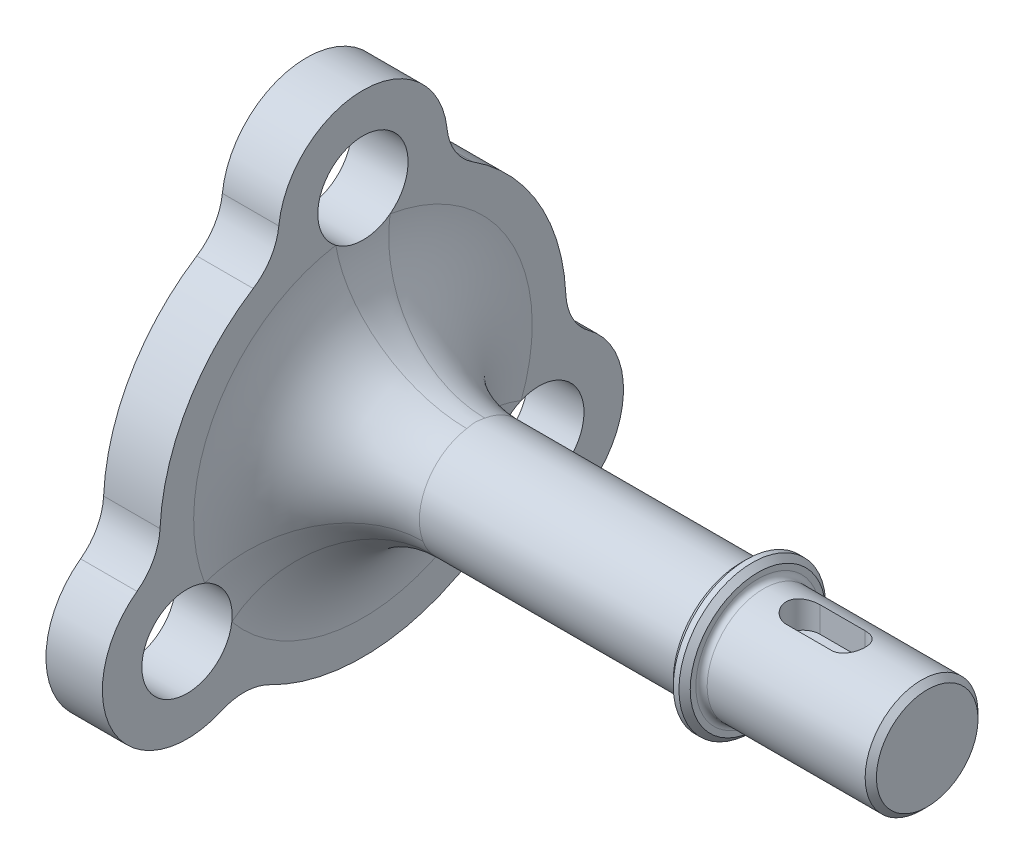
SolidWorks part; units mm, degrees
ref_plane "Front Plane" through (0, 0, 0) normal (0, 0, 1) x (1, 0, 0)
ref_plane "Top Plane" through (0, 0, 0) normal (0, 1, 0) x (1, 0, 0)
ref_plane "Right Plane" through (0, 0, 0) normal (1, 0, 0) x (0, 0, -1)
sketch "Sketch1" plane through (0, 0, 0) normal (1, 0, 0) x (0, 0, -1)
  line L0 (-15.5885, -9) -> (0, 18) construction
  line L1 (0, 18) -> (15.5885, -9) construction
  line L2 (15.5885, -9) -> (-13.3467, -9) construction
  circle A1 centre (0, 18) radius 4
  arc A2 (7.4559, 18.8125) -> (-7.4559, 18.8125) centre (0, 18) ccw
  arc A3 (12.5642, -15.8632) -> (20.02, -2.9493) centre (15.5885, -9) ccw
  circle A4 centre (15.5885, -9) radius 4
  arc A5 (-20.02, -2.9493) -> (-12.5642, -15.8632) centre (-15.5885, -9) ccw
  circle A6 centre (-15.5885, -9) radius 4
  arc A7 (-9.725, 15.1467) -> (-17.98, 0.8488) centre (0, 0) ccw
  arc A8 (-8.2549, -15.9955) -> (8.2549, -15.9955) centre (0, 0) ccw
  arc A9 (-7.4559, 18.8125) -> (-9.725, 15.1467) centre (-12.4264, 19.3542) cw
  arc A10 (17.98, 0.8488) -> (9.725, 15.1467) centre (0, 0) ccw
  arc A11 (20.02, -2.9493) -> (17.98, 0.8488) centre (22.9744, 1.0845) cw
  arc A12 (-20.02, -2.9493) -> (-17.98, 0.8488) centre (-22.9744, 1.0845) ccw
  arc A13 (12.5642, -15.8632) -> (8.2549, -15.9955) centre (10.548, -20.4387) ccw
  arc A14 (-12.5642, -15.8632) -> (-8.2549, -15.9955) centre (-10.548, -20.4387) cw
  arc A15 (7.4559, 18.8125) -> (9.725, 15.1467) centre (12.4264, 19.3542) ccw
  point P15 (0, 0)
  point P19 (-7.3354, 16.4375)
  point P22 (17.903, -1.8661)
  point P29 (-10.5676, -14.5714)
  dimension "D2" = 15
  dimension "D3" = 8
  dimension "D6" = 5
  dimension "D7" = 5
  dimension "D5" = 31.1769
  dimension "D4" = 3
extrude "Boss-Extrude1" add sketch "Sketch1" along normal blind 5
sketch "Sketch2" plane through (5, 0, 0) normal (1, 0, 0) x (0, 0, -1)
  circle A0 centre (0, 0) radius 5
  dimension "D1" = 10
extrude "Boss-Extrude2" add sketch "Sketch2" along normal blind 50
sketch "Sketch3" plane through (0, 0, 0) normal (0, 1, 0) x (1, 0, 0)
  line L0 (55, -5) -> (55, 5) construction
  line L1 (38.5, 6.5) -> (40, 6.5)
  line L2 (38.5, 6.5) -> (38.5, 5)
  line L3 (38.5, 5) -> (40, 5)
  line L4 (40, 6.5) -> (40, 5)
  line L5 (38.5, 6.5) -> (40, 5) construction
  line L6 (38.5, 5) -> (40, 6.5) construction
  line L7 (5, 0) -> (55, 0) construction
  line L8 (5, -7.4559) -> (5, 7.4559) construction
  point P0 (39.25, 5.75)
  dimension "D1" = 15
  dimension "D2" = 1.5
  dimension "D3" = 1.5
  dimension "D4" = 5
revolve "Revolve1" add sketch "Sketch3" angle 360 about L7
ref_plane "Plane1" through (0, 5, 0) normal (0, 1, 0) x (1, 0, 0)
sketch "Sketch4" plane through (0, 5, 0) normal (0, 1, 0) x (1, 0, 0)
  line L0 (44, 0) -> (48, 0) construction
  line L5 (44, 1.5) -> (48, 1.5)
  line L6 (44, -1.5) -> (48, -1.5)
  line L7 (55, 5) -> (40, 5) construction
  line L8 (55, -5) -> (55, 5) construction
  arc A2 (44, 1.5) -> (44, -1.5) centre (44, 0) ccw
  arc A3 (48, -1.5) -> (48, 1.5) centre (48, 0) ccw
  point P3 (46, 0)
  dimension "D1" = 1.5
  dimension "D2" = 4
  dimension "D3" = 5
  dimension "D4" = 9
extrude "Cut-Extrude1" cut sketch "Sketch4" against normal blind 2.5
fillet "Fillet2" radius 0.5 2 edges at (38.5, 0, -5) (40, 0, 5)
chamfer "Chamfer1" distance 0.5 angle 45 2 edges at (40, 0, 6.5) (38.5, 0, 6.5)
chamfer "Chamfer2" distance 0.5 angle 45 1 edges at (55, 0, -5)
fillet "Fillet3" radius 10 1 edges at (5, 0, 5)
